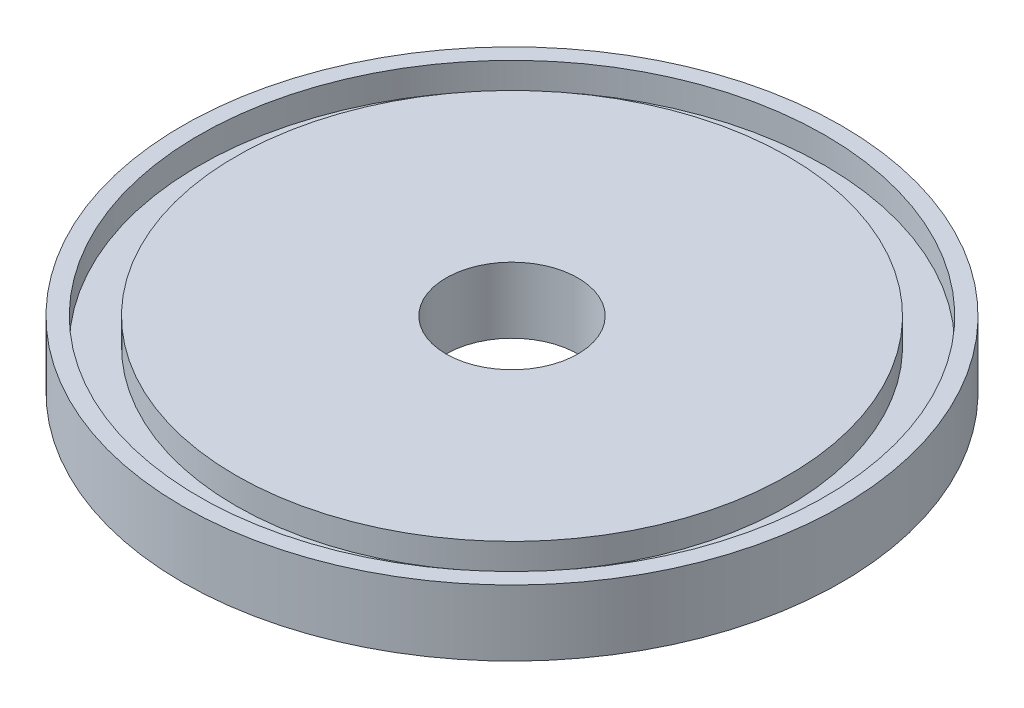
SolidWorks part; units mm, degrees
ref_plane "Front Plane" through (0, 0, 0) normal (0, 0, 1) x (1, 0, 0)
ref_plane "Top Plane" through (0, 0, 0) normal (0, 1, 0) x (1, 0, 0)
ref_plane "Right Plane" through (0, 0, 0) normal (1, 0, 0) x (0, 0, -1)
sketch "Sketch1" plane through (0, 0, 0) normal (0, 0, 1) x (1, 0, 0)
  line L0 (-26.6065, 6.35) -> (-26.6065, 3.81)
  line L1 (0, 0) -> (-31.75, 0)
  line L2 (0, 0) -> (0, 6.35)
  line L3 (0, 6.35) -> (-26.6065, 6.35)
  line L4 (-31.75, 0) -> (-31.75, 6.35)
  line L5 (-26.6065, 3.81) -> (-30.1625, 3.81)
  line L6 (-30.1625, 3.81) -> (-30.1625, 6.35)
  line L7 (-30.1625, 6.35) -> (-31.75, 6.35)
  dimension "D1" = 6.35
  dimension "D2" = 31.75
  dimension "D3" = 2.54
  dimension "D4" = 3.556
  dimension "D5" = 1.5875
revolve "Revolve1" add sketch "Sketch1" angle 360 about L2
hole_wizard "1/2 (0.5) Diameter Hole1" positions "Sketch2" profile "Sketch3" hole size "1/2" standard "ANSI Inch" end condition through all
sketch "Sketch2" plane through (0, 6.35, 0) normal (0, 1, 0) x (1, 0, 0)
  point P0 (0, 0)
sketch "Sketch3" plane through (0, 6.35, 0) normal (1, 0, 0) x (0, 0, 1)
  line L0 (0, 0) -> (0, 6.35)
  line L1 (0, 6.35) -> (6.35, 6.35)
  line L2 (6.35, 6.35) -> (6.35, 0)
  line L5 (6.35, 0) -> (0, 0)
  line L11 (0, -6.35) -> (0, 107.95) construction
  dimension "Thru Hole Dia." = 12.7
  dimension "Thru Hole Depth" = 6.35
